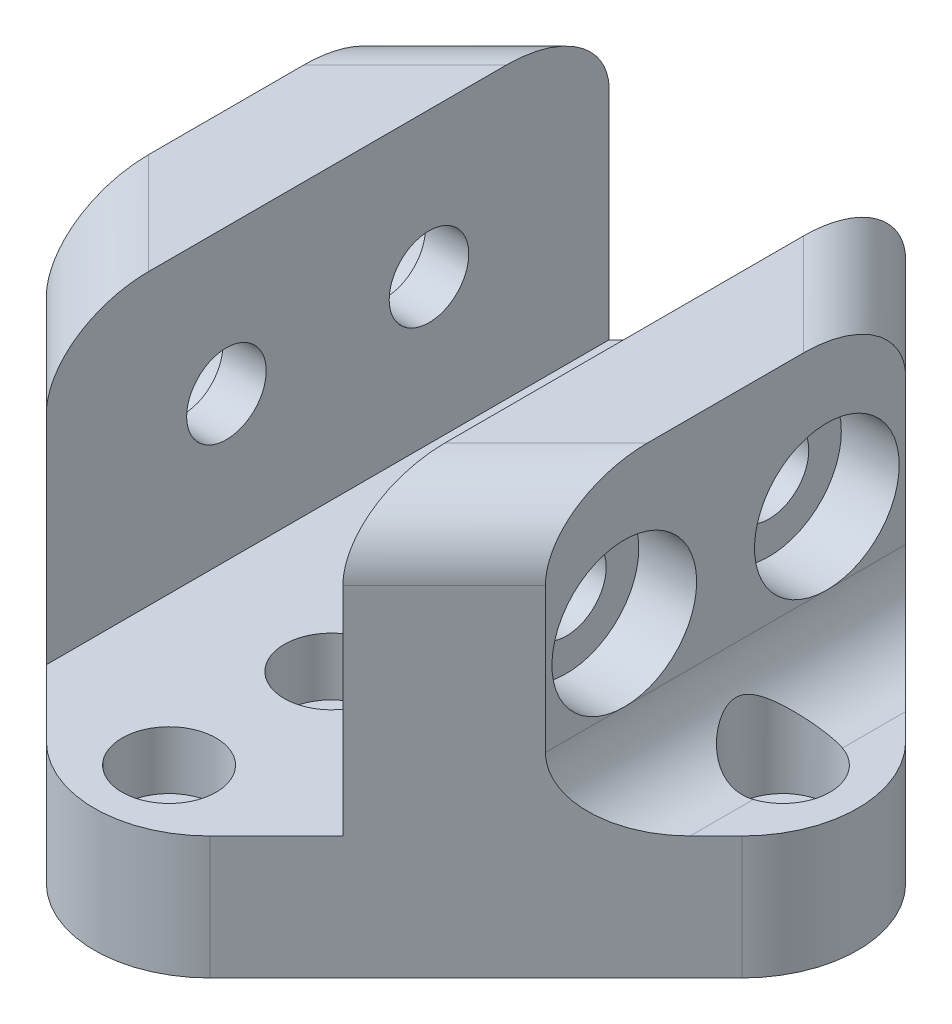
SolidWorks part; units mm, degrees
ref_plane "Спереди" through (0, 0, 0) normal (0, 0, 1) x (1, 0, 0)
ref_plane "Сверху" through (0, 0, 0) normal (0, 1, 0) x (1, 0, 0)
ref_plane "Справа" through (0, 0, 0) normal (1, 0, 0) x (0, 0, -1)
sketch "Эскиз1" plane through (0, 0, 0) normal (0, 1, 0) x (1, 0, 0)
  line L4 (0, 0) -> (29.6985, 0) construction
  line L5 (5.6569, -24.0416) -> (24.0416, -5.6569)
  line L6 (24.0416, 5.6569) -> (5.6569, 24.0416)
  line L7 (-5.6569, 24.0416) -> (-24.0416, 5.6569)
  line L8 (-24.0416, -5.6569) -> (-5.6569, -24.0416)
  line L10 (21.2132, 0) -> (0, 21.2132) construction
  line L11 (0, 21.2132) -> (-21.2132, 0) construction
  line L12 (-21.2132, 0) -> (0, -21.2132) construction
  line L13 (0, -21.2132) -> (21.2132, 0) construction
  line L14 (0, 10) -> (-10, 0) construction
  line L15 (-10, 0) -> (0, -10) construction
  line L16 (0, -10) -> (10, 0) construction
  line L17 (10, 0) -> (0, 10) construction
  circle A0 centre (0, 0) radius 21 construction
  circle A1 centre (21.2132, 0) radius 1.75
  circle A2 centre (10, 0) radius 1.75 construction
  circle A3 centre (0, -10) radius 1.75
  circle A4 centre (0, -21.2132) radius 1.75
  circle A5 centre (-10, 0) radius 1.75 construction
  circle A6 centre (-21.2132, 0) radius 1.75
  circle A7 centre (0, 10) radius 1.75
  circle A8 centre (0, 21.2132) radius 1.75
  circle A11 centre (0, 0) radius 15 construction
  circle A12 centre (0, 0) radius 7.0711 construction
  arc A13 (24.0416, 5.6569) -> (24.0416, -5.6569) centre (18.3848, 0) cw
  arc A14 (5.6569, -24.0416) -> (-5.6569, -24.0416) centre (0, -18.3848) cw
  arc A15 (-24.0416, -5.6569) -> (-24.0416, 5.6569) centre (-18.3848, 0) cw
  arc A16 (-5.6569, 24.0416) -> (5.6569, 24.0416) centre (0, 18.3848) cw
  point P36 (-29.6985, 0)
  point P39 (0, 29.6985)
  dimension "D2" = 3.5
  dimension "D3" = 3.5
  dimension "D5" = 30
  dimension "D7" = 8
  dimension "D1" = 42
  dimension "D6" = 20
  dimension "D4" = 4
extrude "Бобышка-Вытянуть1" add sketch "Эскиз1" along normal blind 8.5
sketch "Эскиз2" plane through (0, 8.5, 0) normal (0, 1, 0) x (1, 0, 0)
  line L5 (-10.25, 19.4485) -> (-10.25, -19.4485)
  line L6 (-5.6569, 24.0416) -> (-24.0416, 5.6569) construction
  line L7 (-24.0416, -5.6569) -> (-5.6569, -24.0416) construction
  line L8 (-10.25, -19.4485) -> (-17.25, -12.4485)
  line L9 (-17.25, -12.4485) -> (-17.25, 12.4485)
  line L10 (-17.25, 12.4485) -> (-10.25, 19.4485)
  line L11 (0, 0) -> (0, 26.3848) construction
  line L12 (17.25, 12.4485) -> (10.25, 19.4485)
  line L13 (17.25, -12.4485) -> (17.25, 12.4485)
  line L14 (10.25, -19.4485) -> (17.25, -12.4485)
  line L15 (10.25, 19.4485) -> (10.25, -19.4485)
  arc A0 (5.6569, 24.0416) -> (-5.6569, 24.0416) centre (0, 18.3848) ccw construction
  dimension "D1" = 20.5
  dimension "D2" = 7
extrude "Бобышка-Вытянуть2" add sketch "Эскиз2" along normal blind 20
sketch "Эскиз3" plane through (17.25, 0, 0) normal (1, 0, 0) x (0, 0, -1)
  line L0 (-12.4485, 18.5) -> (12.4485, 18.5) construction
  line L1 (-12.4485, 28.5) -> (-12.4485, 8.5) construction
  line L2 (12.4485, 28.5) -> (12.4485, 8.5) construction
  line L3 (0, 18.5) -> (0, 28.5) construction
  line L4 (-12.4485, 28.5) -> (12.4485, 28.5) construction
  circle A0 centre (-7, 18.5) radius 2.75
  circle A1 centre (7, 18.5) radius 2.75
  dimension "D1" = 5.5
  dimension "D2" = 14
extrude "Вырез-Вытянуть1" cut sketch "Эскиз3" against normal through all
sketch "Эскиз4" plane through (17.25, 0, 0) normal (1, 0, 0) x (0, 0, -1)
  circle A0 centre (-7, 18.5) radius 5
  circle A1 centre (7, 18.5) radius 5
  dimension "D1" = 10
  dimension "D2" = 10
extrude "Вырез-Вытянуть2" cut sketch "Эскиз4" against normal blind 4
mirror "Зеркальное отражение1" about plane through (0, 0, 0) normal (1, 0, 0) of "Вырез-Вытянуть2"
sketch "Эскиз5" plane through (0, 8.5, 0) normal (0, 1, 0) x (1, 0, 0)
  circle A0 centre (0, 21.2132) radius 3.25
  circle A1 centre (0, 10) radius 3.25
  circle A2 centre (0, -10) radius 3.25
  circle A3 centre (0, -21.2132) radius 3.25
  circle A4 centre (21.2132, 0) radius 3.25
  circle A5 centre (-21.2132, 0) radius 3.25
  dimension "D1" = 6.5
  dimension "D2" = 6.5
  dimension "D3" = 6.5
  dimension "D4" = 6.5
  dimension "D5" = 6.5
  dimension "D6" = 6.5
extrude "Вырез-Вытянуть3" cut sketch "Эскиз5" against normal blind 4
fillet "Скругление2" radius 5 6 edges at (-13.75, 28.5, -15.9485) (-13.75, 28.5, 15.9485) (13.75, 28.5, -15.9485) (13.75, 28.5, 15.9485) (17.25, 8.5, 0) (-17.25, 8.5, 0)
equation "\"print_offset\"= 0.5"
equation "\"tape_width\"=51"
equation "\"tape_thikness\"=5"
equation "\"tape_distance\"=5"
equation "\"screw_d\"=3"
equation "\"screw_hh_d\"=5.3"
equation "\"nut_d\"=5.5"
equation "\"nut_h\"=2.5"
equation "\"sitting_screws\"=30"
equation "\"mount_size\"=42"
equation "\"D1@Эскиз1\"=\"mount_size\""
equation "\"D2@Эскиз1\"=\"screw_d\"+\"print_offset\""
equation "\"D3@Эскиз1\"=\"D2@Эскиз1\""
equation "\"D5@Эскиз1\"=\"sitting_screws\""
equation "\"D1@Эскиз2\"=\"print_offset\"+20"
equation "\"D1@Эскиз3\"=\"print_offset\"+5"
equation "\"D2@Эскиз4\"=\"D1@Эскиз4\""
equation "\"D2@Эскиз5\"=\"D1@Эскиз5\""
equation "\"D3@Эскиз5\"=\"D1@Эскиз5\""
equation "\"D4@Эскиз5\"=\"D1@Эскиз5\""
equation "\"D5@Эскиз5\"=\"D1@Эскиз5\""
equation "\"D6@Эскиз5\"=\"D1@Эскиз5\""
